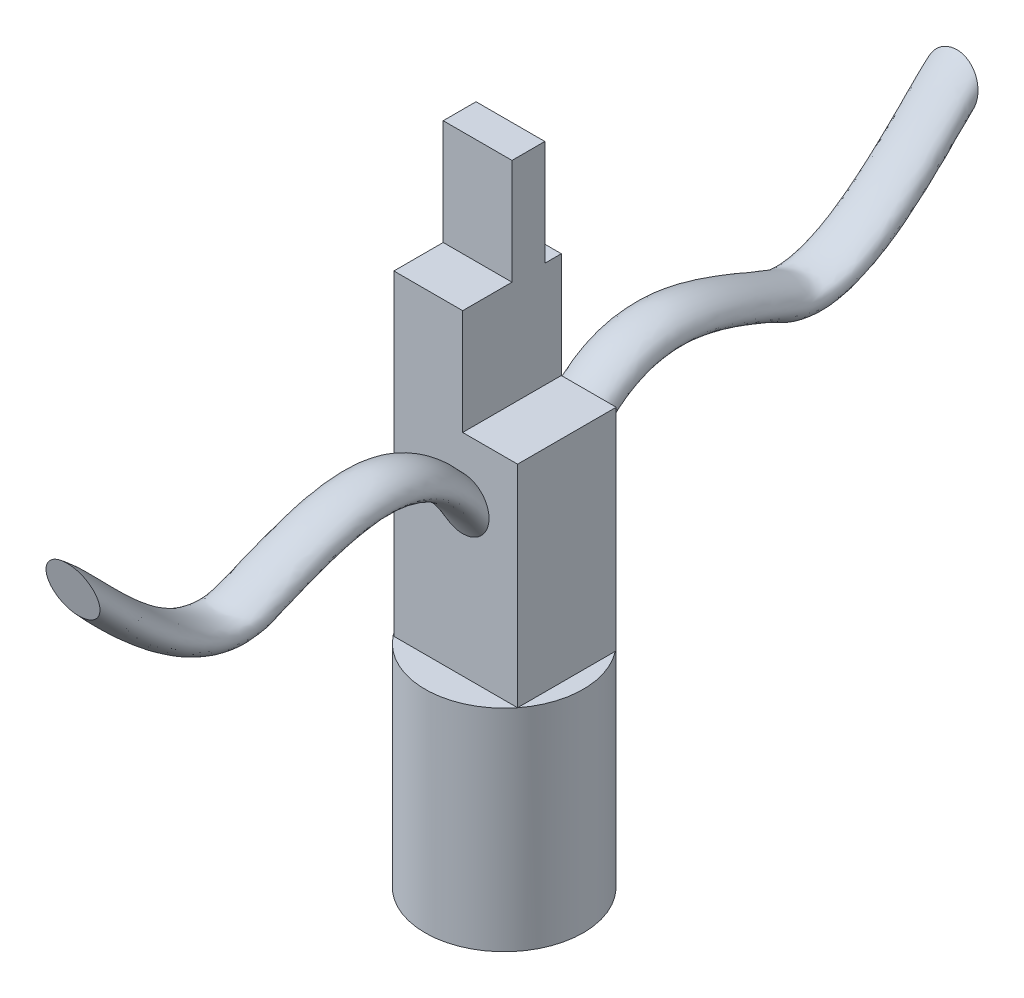
SolidWorks part; units mm, degrees
ref_plane "Front Plane" through (0, 0, 0) normal (0, 0, 1) x (1, 0, 0)
ref_plane "Top Plane" through (0, 0, 0) normal (0, 1, 0) x (1, 0, 0)
ref_plane "Right Plane" through (0, 0, 0) normal (1, 0, 0) x (0, 0, -1)
sketch "Sketch2" plane through (0, 0, 0) normal (0, 1, 0) x (1, 0, 0)
  circle A0 centre (-70.7604, -16.8858) radius 762
extrude "Boss-Extrude1" add sketch "Sketch2" along normal blind 2032
sketch "Sketch3" plane through (0, 2032, 0) normal (0, 1, 0) x (1, 0, 0)
  line L1 (-662.6916, 462.9698) -> (528.7394, 462.9698)
  line L2 (-662.6916, 462.9698) -> (-662.6916, -487.2517)
  line L3 (-662.6916, -487.2517) -> (528.7394, -487.2517)
  line L4 (528.7394, 462.9698) -> (528.7394, -487.2517)
  circle A0 centre (-70.7604, -16.8858) radius 762 construction
extrude "Boss-Extrude2" add sketch "Sketch3" along normal blind 2032
sketch "Sketch8" plane through (0, 0, -462.9698) normal (0, 0, -1) x (-1, 0, 0)
  line L0 (662.6916, 4064) -> (-528.7394, 4064) construction
  circle A0 centre (0, 3473.5458) radius 254
sketch "Sketch9" plane through (0, 4064, 0) normal (0, 1, 0) x (1, 0, 0)
  line L0 (-662.6916, -487.2517) -> (528.7394, -487.2517) construction
  line L1 (0, -487.2517) -> (-662.6916, -487.2517)
  line L2 (0, -487.2517) -> (0, 462.9698)
  line L3 (0, 462.9698) -> (-662.6916, 462.9698)
  line L4 (-662.6916, -487.2517) -> (-662.6916, 462.9698)
  line L5 (528.7394, 462.9698) -> (-662.6916, 462.9698) construction
extrude "Boss-Extrude4" add sketch "Sketch9" along normal blind 1016
sketch "Sketch10" plane through (0, 0, 0) normal (1, 0, 0) x (0, 0, -1)
  spline S0 degree 3 poles (462.9698, 3473.5458) (1058.046, 4323.3718) (1835.2559, 3977.0259) (3157.887, 3446.6255) (3890.1797, 4333.6867) (4216.6457, 4629.9811) knots 0 0 0 0 0.513368 0.547212 1 1 1 1
sweep "Sweep5" add profiles "Sketch8" path "Sketch10"
fillet "Fillet1" radius 2.54 1 edges at (-662.6916, 3556, 487.2517)
sketch "Sketch14" plane through (0, 5080, 0) normal (0, 1, 0) x (1, 0, 0)
  line L0 (0, -487.2517) -> (0, 462.9698) construction
  line L1 (0, -12.1409) -> (-662.6916, -12.1409)
  line L2 (0, -12.1409) -> (0, 304.1604)
  line L3 (0, 304.1604) -> (-662.6916, 304.1604)
  line L4 (-662.6916, -12.1409) -> (-662.6916, 304.1604)
  line L5 (-662.6916, 462.9698) -> (-662.6916, -484.7117) construction
extrude "Boss-Extrude6" add sketch "Sketch14" along normal blind 1016
mirror "Mirror1" about plane through (0, 6096, 12.1409) normal (0, 0, -1) of "Sweep5"
